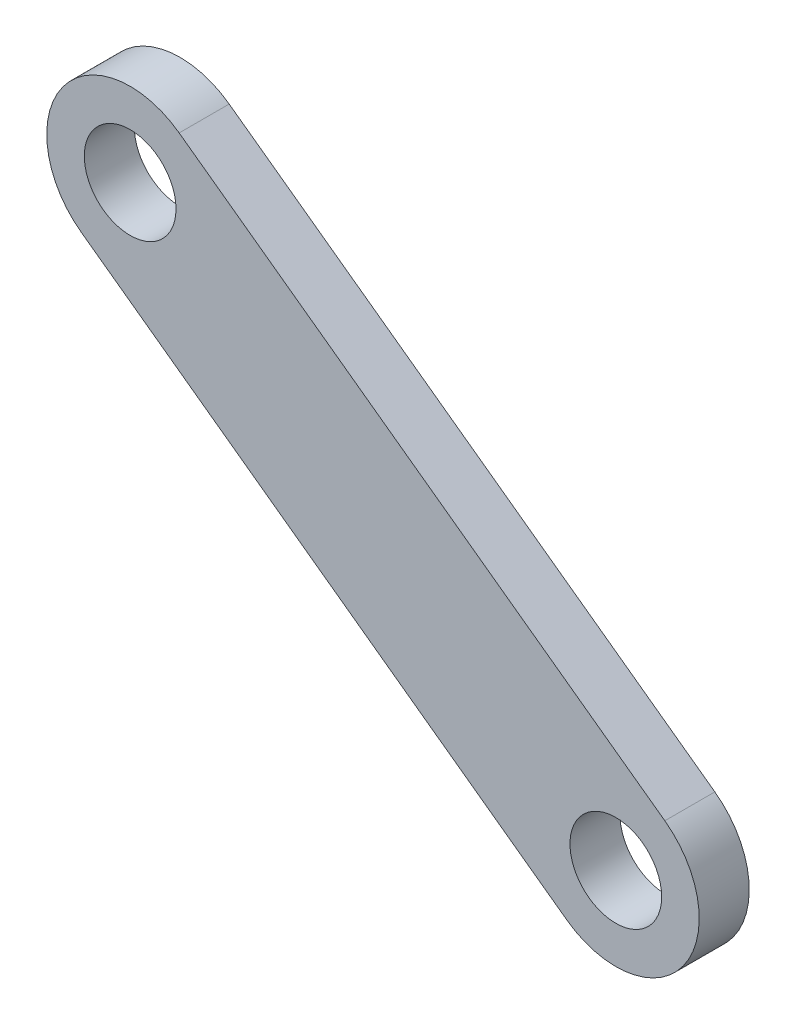
SolidWorks part; units mm, degrees
material "Acrylic (Medium-high impact)"
ref_plane "Front Plane" through (0, 0, 0) normal (0, 0, 1) x (1, 0, 0)
ref_plane "Top Plane" through (0, 0, 0) normal (0, 1, 0) x (1, 0, 0)
ref_plane "Right Plane" through (0, 0, 0) normal (1, 0, 0) x (0, 0, -1)
sketch "Sketch1" plane through (0, 0, 0) normal (0, 0, 1) x (1, 0, 0)
  line L0 (0, 0) -> (46.2353, -33.5919) construction
  line L1 (4.6655, 6.4216) -> (50.9009, -27.1704)
  line L2 (-4.6655, -6.4216) -> (41.5698, -40.0135)
  line L3 (0, 0) -> (33.1227, 0) construction
  arc A0 (4.6655, 6.4216) -> (-4.6655, -6.4216) centre (0, 0) ccw
  arc A1 (41.5698, -40.0135) -> (50.9009, -27.1704) centre (46.2353, -33.5919) ccw
  point P3 (23.1177, -16.796)
  dimension "D2" = 7.9375
  dimension "D1" = 57.15
  dimension "D3" = 36
extrude "Boss-Extrude1" add sketch "Sketch1" along normal blind 4.7625
hole_wizard "5/16 Clearance Hole1" positions "Sketch2" profile "Sketch3" hole size "5/16" standard "ANSI Inch" end condition through all
sketch "Sketch2" plane through (0, 0, 4.7625) normal (0, 0, 1) x (1, 0, 0)
  point P0 (0, 0)
  point P4 (46.2353, -33.5919)
sketch "Sketch3" plane through (0, 0, 4.7625) normal (1, 0, 0) x (0, -1, 0)
  line L0 (0, 0) -> (0, 4.7625)
  line L1 (0, 4.7625) -> (4.365, 4.7625)
  line L2 (4.365, 4.7625) -> (4.365, 0)
  line L5 (4.365, 0) -> (0, 0)
  line L11 (0, -6.35) -> (0, 107.95) construction
  dimension "Thru Hole Dia." = 8.73
  dimension "Thru Hole Depth" = 4.7625
hole_wizard "5/16 Clearance Hole2" positions "Sketch6" profile "Sketch7" hole size "5/16" standard "ANSI Inch"
sketch "Sketch6" plane through (-478.1158, -1361.1994, 4.7625) normal (0, 0, 1) x (0.9365, 0.3507, 0)
  point P0 (956.6255, 1059.4117)
sketch "Sketch7" plane through (46.2353, -33.5919, 4.7625) normal (1, 0, 0) x (0, -1, 0)
  line L0 (0, 0) -> (0, 53.4228)
  line L1 (0, 53.4228) -> (4.365, 50.8)
  line L2 (4.365, 50.8) -> (4.365, 0)
  line L3 (4.365, 0) -> (0, 0)
  line L4 (0, 53.4228) -> (-4.365, 50.8) construction
  line L5 (0, -6.35) -> (0, 107.95) construction
  dimension "Hole Dia." = 8.73
  dimension "Hole Depth" = 50.8
  dimension "Drill Angle" = 118
